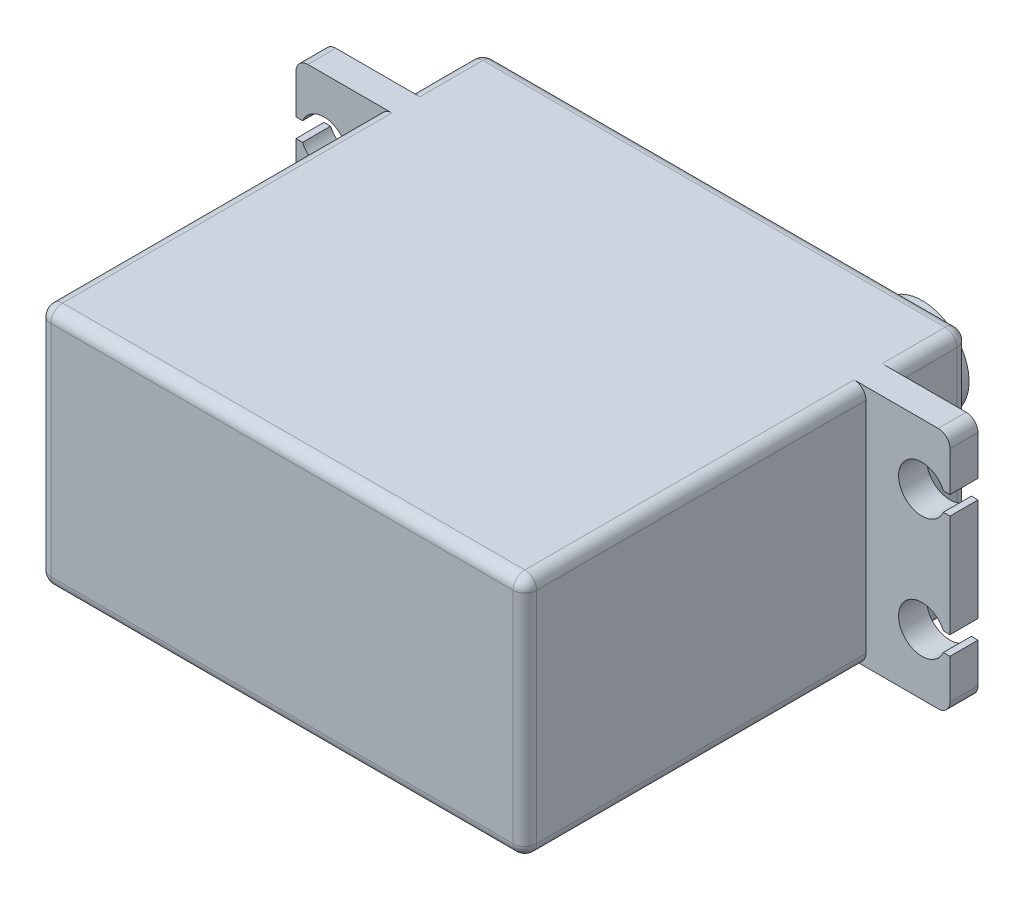
SolidWorks part; units mm, degrees
ref_plane "Front Plane" through (0, 0, 0) normal (0, 0, 1) x (1, 0, 0)
ref_plane "Top Plane" through (0, 0, 0) normal (0, 1, 0) x (1, 0, 0)
ref_plane "Right Plane" through (0, 0, 0) normal (1, 0, 0) x (0, 0, -1)
sketch "Sketch1" plane through (0, 0, 0) normal (0, 1, 0) x (1, 0, 0)
  line L0 (-41.275, 28.9719) -> (0, 28.9719) construction
  line L1 (0, 0) -> (-41.275, 0)
  line L2 (0, 0) -> (0, 28.9719)
  line L3 (0, 37.7031) -> (-41.275, 37.7031)
  line L4 (-41.275, 0) -> (-41.275, 28.9719)
  line L5 (-20.6375, 37.7031) -> (-20.6375, 0) construction
  line L6 (0, 28.9719) -> (7.1437, 28.9719)
  line L7 (-41.275, 31.3531) -> (-48.4187, 31.3531)
  line L8 (0, 31.3531) -> (0, 37.7031)
  line L9 (-41.275, 28.9719) -> (-48.4187, 28.9719)
  line L10 (-48.4187, 31.3531) -> (-48.4187, 28.9719)
  line L11 (7.1437, 31.3531) -> (7.1437, 28.9719)
  line L12 (0, 31.3531) -> (7.1437, 31.3531)
  line L13 (-41.275, 31.3531) -> (-41.275, 37.7031)
  dimension "D1" = 41.275
  dimension "D2" = 37.7031
  dimension "D3" = 28.9719
  dimension "D4" = 7.1437
  dimension "D5" = 2.3813
extrude "Boss-Extrude1" add sketch "Sketch1" along normal blind 20.6375
sketch "Sketch2" plane through (0, 0, -31.3531) normal (0, 0, -1) x (-1, 0, 0)
  line L0 (-7.1437, 10.3187) -> (48.4187, 10.3187) construction
  line L1 (-7.1437, 20.6375) -> (-7.1437, 0) construction
  line L2 (48.4187, 20.6375) -> (48.4187, 0) construction
  line L3 (0, 20.6375) -> (0, 0) construction
  line L4 (20.6375, 20.6375) -> (20.6375, 0) construction
  line L5 (0, 20.6375) -> (41.275, 20.6375) construction
  line L6 (0, 0) -> (41.275, 0) construction
  line L7 (-4.7625, 15.4781) -> (46.0375, 15.4781) construction
  line L8 (-7.1437, 16.2719) -> (-6.5812, 16.2719)
  line L9 (-7.1437, 14.6844) -> (-6.5812, 14.6844)
  line L10 (47.8562, 16.2719) -> (48.4187, 16.2719)
  line L11 (47.8562, 14.6844) -> (48.4187, 14.6844)
  line L12 (48.4187, 14.6844) -> (48.4187, 16.2719)
  line L13 (-7.1437, 14.6844) -> (-7.1437, 16.2719)
  line L14 (47.8562, 4.3656) -> (48.4187, 4.3656)
  line L15 (48.4187, 5.9531) -> (48.4187, 4.3656)
  line L16 (47.8562, 5.9531) -> (48.4187, 5.9531)
  line L17 (-7.1437, 5.9531) -> (-6.5812, 5.9531)
  line L18 (-7.1437, 5.9531) -> (-7.1437, 4.3656)
  line L19 (-7.1437, 4.3656) -> (-6.5812, 4.3656)
  arc A0 (-6.5812, 14.6844) -> (-6.5812, 16.2719) centre (-4.7625, 15.4781) ccw
  arc A1 (-6.5812, 5.9531) -> (-6.5812, 4.3656) centre (-4.7625, 5.1594) cw
  arc A2 (47.8562, 14.6844) -> (47.8562, 16.2719) centre (46.0375, 15.4781) cw
  arc A3 (47.8562, 5.9531) -> (47.8562, 4.3656) centre (46.0375, 5.1594) ccw
  dimension "D1" = 3.9688
  dimension "D2" = 5.1594
  dimension "D3" = 4.7625
  dimension "D4" = 0.7937
extrude "Cut-Extrude1" cut sketch "Sketch2" against normal through all
fillet "Fillet1" radius 1 4 edges at (-48.4187, 20.6375, -30.1625) (-48.4187, 0, -30.1625) (7.1437, 0, -30.1625) (7.1437, 20.6375, -30.1625)
fillet "Fillet2" radius 1 16 edges at (-20.6375, 0, -37.7031) (-20.6375, 20.6375, -37.7031) (-41.275, 10.3187, -37.7031) (0, 10.3187, -37.7031) (-41.275, 0, -34.5281) (-41.275, 20.6375, -34.5281) (0, 0, -34.5281) (0, 20.6375, -34.5281) (0, 0, -14.4859) (0, 20.6375, -14.4859) (0, 10.3187, 0) (-20.6375, 20.6375, 0) (-20.6375, 0, 0) (-41.275, 10.3187, 0) (-41.275, 20.6375, -14.4859) (-41.275, 0, -14.4859)
sketch "Sketch3" plane through (0, 0, -37.7031) normal (0, 0, -1) x (-1, 0, 0)
  line L0 (1, 10.3187) -> (40.275, 10.3187) construction
  line L1 (1, 19.6375) -> (1, 1) construction
  line L2 (40.275, 1) -> (40.275, 19.6375) construction
  circle A0 centre (10.2869, 10.3187) radius 4.7625
  dimension "D1" = 9.525
  dimension "D2" = 9.2869
extrude "Boss-Extrude2" add sketch "Sketch3" along normal blind 3.175
fillet "Fillet3" radius 1 1 edges at (-5.5244, 10.3187, -37.7031)
sketch "Sketch4" plane through (0, 0, -40.8781) normal (0, 0, -1) x (-1, 0, 0)
  circle A0 centre (10.2869, 10.3187) radius 3.9688
  dimension "D1" = 7.9375
extrude "Boss-Extrude3" add sketch "Sketch4" along normal blind 3.175
